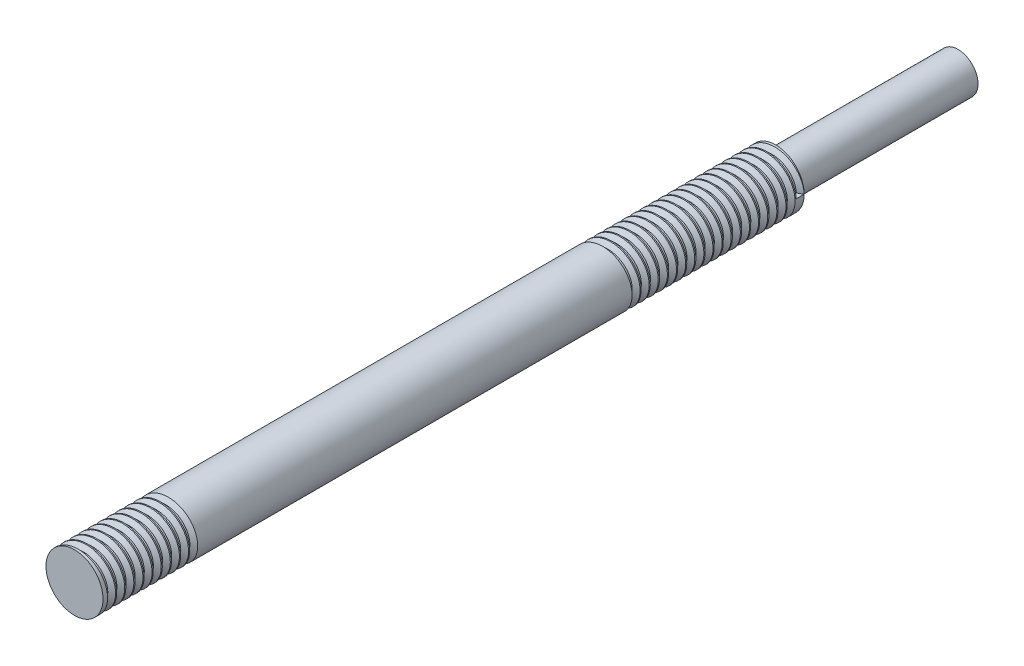
SolidWorks part; units mm, degrees
ref_plane "Front Plane" through (0, 0, 0) normal (0, 0, 1) x (1, 0, 0)
ref_plane "Top Plane" through (0, 0, 0) normal (0, 1, 0) x (1, 0, 0)
ref_plane "Right Plane" through (0, 0, 0) normal (1, 0, 0) x (0, 0, -1)
sketch "Sketch1" plane through (0, 0, 0) normal (0, 0, 1) x (1, 0, 0)
  circle A0 centre (0, 0) radius 2.5
  dimension "D1" = 5
extrude "Boss-Extrude1" add sketch "Sketch1" along normal blind 61.5
sketch "Sketch2" plane through (0, 0, 0) normal (0, 0, -1) x (-1, 0, 0)
  circle A0 centre (0, 0) radius 1.75
  dimension "D1" = 3.5
extrude "Boss-Extrude2" add sketch "Sketch2" along normal blind 16
thread "Thread1" pitch 0.8 method cut profile "Thread Profile1" start angle 0, offset 0, length 8, pitch 0.8, diameter 5
ref_plane "Plane1" through (-2.5, 0, 61.5) normal (0, -1, 0) x (-1, 0, 0)
sketch "Thread Profile1" plane through (-2.5, 0, 61.5) normal (0, -1, 0) x (-1, 0, 0)
  line L0 (0, 0) -> (0, 0.8) construction
  line L11 (0, 0) -> (0, 0.7)
  line L12 (0, 0.7) -> (-0.433, 0.45)
  line L13 (-0.433, 0.45) -> (-0.433, 0.25)
  line L15 (-0.433, 0.25) -> (0, 0)
  line L17 (-0.433, 0.35) -> (0, 0.35) construction
  point P2 (0, 0)
  dimension "Pitch" = 0.8
  dimension "Profile_Angle" = 60
  dimension "Profile_Land" = 0.2
  dimension "Profile_Height" = 0.433
thread "Thread2" pitch 0.8 method cut profile "Thread Profile2" start angle 0, offset 0, length 15, pitch 0.8, diameter 5
ref_plane "Plane2" through (2.5, 0, 0) normal (0, -1, 0) x (1, 0, 0)
sketch "Thread Profile2" plane through (2.5, 0, 0) normal (0, -1, 0) x (1, 0, 0)
  line L0 (0, 0) -> (0, 0.8) construction
  line L11 (0, 0) -> (0, 0.7)
  line L12 (0, 0.7) -> (-0.433, 0.45)
  line L13 (-0.433, 0.45) -> (-0.433, 0.25)
  line L15 (-0.433, 0.25) -> (0, 0)
  line L17 (-0.433, 0.35) -> (0, 0.35) construction
  point P2 (0, 0)
  dimension "Pitch" = 0.8
  dimension "Profile_Angle" = 60
  dimension "Profile_Land" = 0.2
  dimension "Profile_Height" = 0.433
